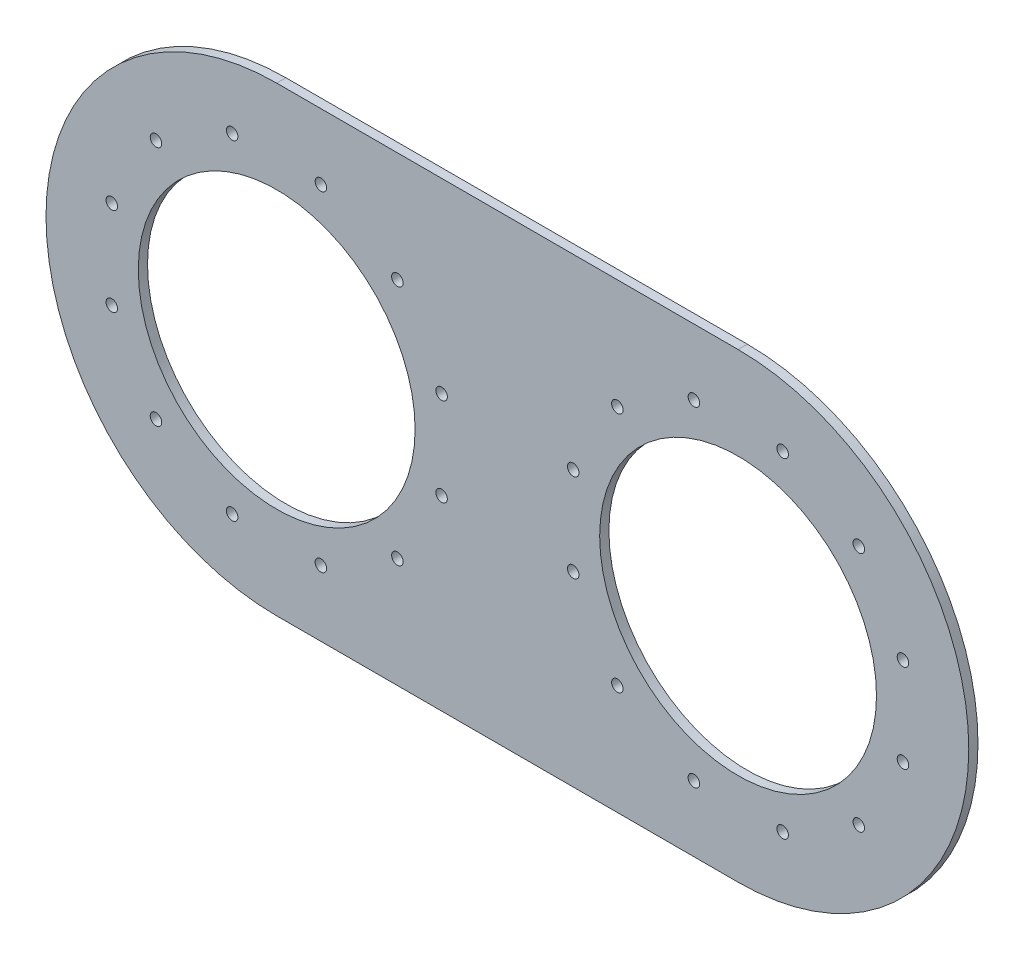
SolidWorks part; units mm, degrees
ref_plane "前视基准面" through (0, 0, 0) normal (0, 0, 1) x (1, 0, 0)
ref_plane "上视基准面" through (0, 0, 0) normal (0, 1, 0) x (1, 0, 0)
ref_plane "右视基准面" through (0, 0, 0) normal (1, 0, 0) x (0, 0, -1)
sketch "草图1" plane through (0, 0, 0) normal (0, 0, 1) x (1, 0, 0)
  line L0 (-50, 50) -> (50, 50)
  line L1 (-50, -50) -> (50, -50)
  arc A2 (50, 50) -> (50, -50) centre (50, 0) cw
  arc A3 (-50, 50) -> (-50, -50) centre (-50, 0) ccw
  circle A4 centre (-50, 0) radius 30
  circle A5 centre (50, 0) radius 30
extrude "凸台-拉伸1" add sketch "草图1" along normal blind 2
hole_wizard "M3 螺纹孔的螺纹孔钻头1" positions "3D草图1" profile "草图2" hole size "M3" standard "ISO" end condition through all
sketch3d "3D草图1"
  point P182 (-40.4237, 35.7393, 2)
  point P184 (-23.837, 26.163, 2)
  point P186 (-14.2607, 9.5763, 2)
  point P211 (-59.6568, 35.7176, 2)
  point P213 (-76.163, 26.163, 2)
  point P215 (-85.7393, 9.5763, 2)
  point P217 (-85.7393, 9.5763, 2)
  point P218 (-76.163, 26.163, 2)
  point P219 (-59.6568, 35.7176, 2)
  point P220 (85.7393, 9.5763, 2)
  point P221 (76.163, 26.163, 2)
  point P222 (59.6568, 35.7176, 2)
  point P223 (14.2607, 9.5763, 2)
  point P224 (23.837, 26.163, 2)
  point P225 (40.4237, 35.7393, 2)
  point P226 (40.4237, -35.7393, 2)
  point P227 (23.837, -26.163, 2)
  point P228 (14.2607, -9.5763, 2)
  point P229 (59.6568, -35.7176, 2)
  point P230 (76.163, -26.163, 2)
  point P231 (85.7393, -9.5763, 2)
  point P232 (-85.7393, -9.5763, 2)
  point P233 (-76.163, -26.163, 2)
  point P234 (-59.6568, -35.7176, 2)
  point P235 (-14.2607, -9.5763, 2)
  point P236 (-23.837, -26.163, 2)
  point P237 (-40.4237, -35.7393, 2)
sketch "草图2" plane through (-40.4237, 35.7393, 2) normal (1, 0, 0) x (0, -1, 0)
  line L0 (0, 0) -> (0, 2)
  line L1 (0, 2) -> (1.25, 2)
  line L2 (1.25, 2) -> (1.25, 0)
  line L5 (1.25, 0) -> (0, 0)
  line L11 (0, -6.35) -> (0, 107.95) construction
  dimension "通孔孔直径" = 2.5
  dimension "通孔孔深度" = 2
